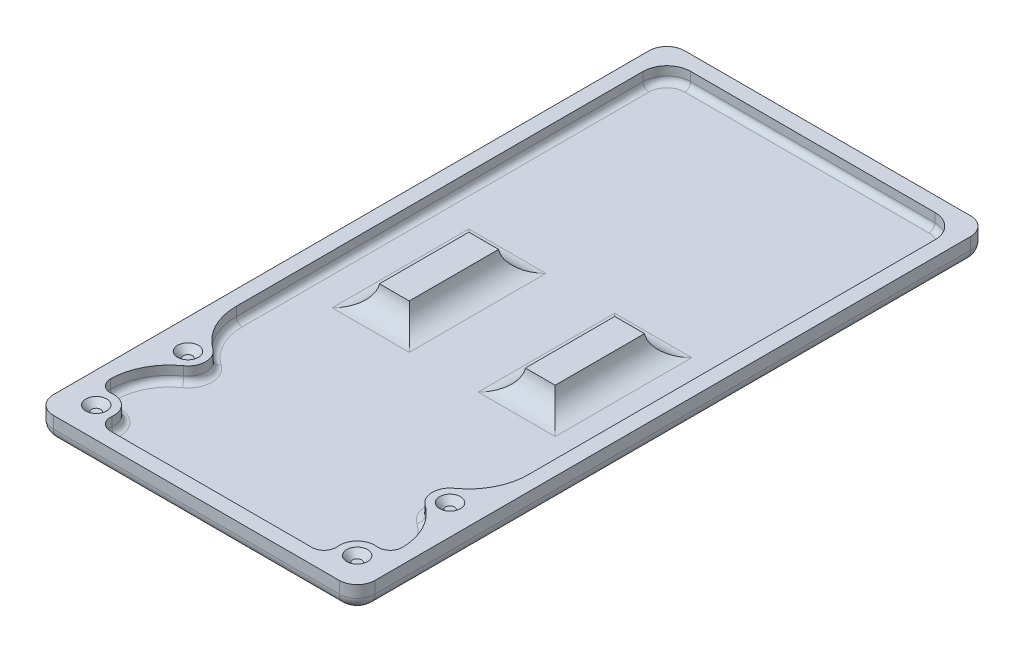
SolidWorks part; units mm, degrees
ref_plane "Front Plane" through (0, 0, 0) normal (0, 0, 1) x (1, 0, 0)
ref_plane "Top Plane" through (0, 0, 0) normal (0, 1, 0) x (1, 0, 0)
ref_plane "Right Plane" through (0, 0, 0) normal (1, 0, 0) x (0, 0, -1)
sketch "Sketch1" plane through (0, 0, 0) normal (0, 1, 0) x (1, 0, 0)
  line L1 (-24.5, -50.5) -> (24.5, -50.5)
  line L2 (-24.5, -50.5) -> (-24.5, 50.5)
  line L3 (-24.5, 50.5) -> (24.5, 50.5)
  line L4 (24.5, -50.5) -> (24.5, 50.5)
  line L5 (-24.5, -50.5) -> (24.5, 50.5) construction
  line L6 (-24.5, 50.5) -> (24.5, -50.5) construction
  point P0 (0, 0)
  dimension "D1" = 49
  dimension "D2" = 101
extrude "Boss-Extrude1" add sketch "Sketch1" along normal blind 1.5
sketch "Sketch2" plane through (0, 0, 0) normal (0, 1, 0) x (1, 0, 0)
  line L4 (24.5, -50.5) -> (24.5, 50.5)
  line L5 (24.5, 50.5) -> (-24.5, 50.5)
  line L6 (-24.5, 50.5) -> (-24.5, -50.5)
  line L7 (-24.5, -50.5) -> (24.5, -50.5)
  line L8 (24.5, -50.5) -> (24.5, 50.5)
  line L9 (24.5, 50.5) -> (-24.5, 50.5)
  line L10 (-24.5, 50.5) -> (-24.5, -50.5)
  line L11 (-24.5, -50.5) -> (24.5, -50.5)
  line L16 (27, -53) -> (27, 53)
  line L17 (27, 53) -> (-27, 53)
  line L18 (-27, 53) -> (-27, -53)
  line L19 (-27, -53) -> (27, -53)
  line L20 (27, -53) -> (27, 53)
  line L21 (27, 53) -> (-27, 53)
  line L22 (-27, 53) -> (-27, -53)
  line L23 (-27, -53) -> (27, -53)
  dimension "D1" = 0
  dimension "D2" = 2.5
extrude "Boss-Extrude2" add sketch "Sketch2" along normal blind 4
sketch "Sketch3" plane through (0, 0, 0) normal (0, 1, 0) x (1, 0, 0)
  line L0 (24.5, -50.5) -> (-24.5, -50.5) construction
  line L2 (-24.5, 50.5) -> (-24.5, -50.5) construction
  line L3 (-24.5, -30.7417) -> (-24.5, -34.0583)
  line L8 (-24.5, -46.4033) -> (-24.5, -50.5)
  line L9 (-24.5, 50.5) -> (-24.5, -50.5) construction
  line L10 (-24.5, -50.5) -> (-20.4033, -50.5)
  line L11 (-24.5, -50.5) -> (24.5, -50.5) construction
  arc A1 (-24.5, -34.0583) -> (-24.5, -30.7417) centre (-22, -32.4) ccw
  arc A2 (-20.4033, -50.5) -> (-24.5, -46.4033) centre (-21.9, -47.9) ccw
  dimension "D5" = 6
  dimension "D1" = 2.6
  dimension "D3" = 2.5
  dimension "D4" = 18.1
extrude "Boss-Extrude3" add sketch "Sketch3" along normal up to surface (4 mm away) up to face at (0, 4, 0)
sketch "Sketch8" plane through (0, 1.5, 0) normal (0, 1, 0) x (1, 0, 0)
  line L0 (0, 0) -> (-24.5, 0) construction
  line L1 (-14.75, 7.5) -> (-9.75, 7.5)
  line L2 (-14.75, 7.5) -> (-14.75, -7.5)
  line L3 (-14.75, -7.5) -> (-9.75, -7.5)
  line L4 (-9.75, 7.5) -> (-9.75, -7.5)
  line L5 (-24.5, 50.5) -> (-24.5, -30.7417) construction
  point P4 (-9.75, 0)
  point P11 (-12.25, 0)
  point P12 (-12.25, 7.5)
  dimension "D1" = 15
  dimension "D2" = 5
extrude "Boss-Extrude4" add sketch "Sketch8" along normal offset from surface (3.5 mm away) 1 up to face at (0, 4, 0) offset beyond the face yes
fillet "Fillet3" radius 4 4 edges at (-12.25, 1.5, -7.5) (-9.75, 1.5, 0) (-14.75, 1.5, 0) (-12.25, 1.5, 7.5)
mirror "Mirror1" about plane through (0, 0, 0) normal (1, 0, 0) of "Fillet3", "Boss-Extrude3", "Boss-Extrude4"
sketch "Sketch4" plane through (0, 4, 0) normal (0, 1, 0) x (1, 0, 0)
  circle A0 centre (-21.9, -47.9) radius 1.75
  circle A1 centre (21.9, -47.9) radius 1.75
  arc A2 (-20.4033, -50.5) -> (-24.5, -46.4033) centre (-21.9, -47.9) ccw construction
  arc A3 (24.5, -46.4033) -> (20.4033, -50.5) centre (21.9, -47.9) ccw construction
  dimension "D1" = 3.5
  dimension "D2" = 3.5
extrude "Cut-Extrude1" cut sketch "Sketch4" against normal blind 1
sketch "Sketch5" plane through (0, 4, 0) normal (0, 1, 0) x (1, 0, 0)
  circle A0 centre (-22, -32.4) radius 1.75
  circle A1 centre (22, -32.4) radius 1.75
  dimension "D1" = 3.5
  dimension "D2" = 3.5
extrude "Cut-Extrude2" cut sketch "Sketch5" against normal blind 1
sketch "Sketch6" plane through (0, 0, 0) normal (0, 1, 0) x (1, 0, 0)
  line L1 (-9, -45) -> (5.5, -45)
  line L2 (-9, -45) -> (-9, -52.3)
  line L3 (-9, -52.3) -> (5.5, -52.3)
  line L4 (5.5, -45) -> (5.5, -52.3)
  line L8 (-20.4033, -50.5) -> (20.4033, -50.5) construction
  line L10 (24.5, -46.4033) -> (24.5, -34.0583) construction
  line L11 (-24.5, -34.0583) -> (-24.5, -46.4033) construction
  line L13 (-27, -53) -> (27, -53) construction
  dimension "D1" = 15.5
  dimension "D2" = 19
  dimension "D3" = 0.7
  dimension "D4" = 5.5
extrude "Cut-Extrude3" [suppressed] cut sketch "Sketch6" along normal through all
sketch "Sketch7" plane through (0, 0, 0) normal (0, 1, 0) x (1, 0, 0)
  line L0 (-27, -53) -> (27, -53) construction
  line L1 (18.3, -47.7) -> (6.5, -47.7)
  line L2 (18.3, -47.7) -> (18.3, -43.7)
  line L3 (18.3, -43.7) -> (6.5, -43.7)
  line L4 (6.5, -47.7) -> (6.5, -43.7)
  line L6 (-27, -53) -> (27, -53) construction
  line L7 (27, -53) -> (27, 53) construction
  point P10 (12.4, -43.7)
  dimension "D1" = 11.8
  dimension "D3" = 9.3
  dimension "D4" = 5.3
  dimension "D5" = 14.6
extrude "Cut-Extrude4" [suppressed] cut sketch "Sketch7" along normal through all
fillet "Fillet1" radius 3 4 edges at (-27, 2, 53) (27, 2, 53) (27, 2, -53) (-27, 2, -53)
fillet "Fillet2" radius 10 4 edges at (24.5, 2.75, 30.7417) (24.5, 2.75, 34.0583) (-24.5, 2.75, 30.7417) (-24.5, 2.75, 34.0583)
chamfer "Chamfer1" distance 1 angle 45 2 edges at (-22, 3, 34.15) (22, 3, 34.15)
chamfer "Chamfer2" distance 1 angle 45 2 edges at (-21.9, 3, 49.65) (21.9, 3, 49.65)
fillet "Fillet4" radius 2 4 edges at (24.5, 2.75, 46.4033) (20.4033, 2.75, 50.5) (-20.4033, 2.75, 50.5) (-24.5, 2.75, 46.4033)
fillet "Fillet6" radius 4 2 edges at (24.5, 2.75, -50.5) (-24.5, 2.75, -50.5)
fillet "Fillet5" radius 1 3 edges at (24.5, 1.5, -12.3592) (0, 1.5, -50.5) (-24.5, 1.5, -12.3592) type face fillet first side face at (12.25, 1.5, 0) second side face at (24.5, 2.75, -12.3592) second side face at (0, 2.75, -50.5) second side face at (-24.5, 2.75, -12.3592)
fillet "Fillet7" radius 2 8 edges at (-26.1213, 0, -52.1213) (0, 0, -53) (26.1213, 0, -52.1213) (27, 0, 0) (26.1213, 0, 52.1213) (0, 0, 53) (-26.1213, 0, 52.1213) (-27, 0, 0)
sketch "Sketch9" plane through (0, 0, 0) normal (0, 1, 0) x (1, 0, 0)
  line L1 (-50, 75) -> (50, 75)
  line L2 (-50, 75) -> (-50, -75)
  line L3 (-50, -75) -> (50, -75)
  line L4 (50, 75) -> (50, -75)
  line L5 (-50, 75) -> (50, -75) construction
  line L6 (-50, -75) -> (50, 75) construction
  point P0 (0, 0)
  dimension "D1" = 150
  dimension "D2" = 100
extrude "Boss-Extrude5" [suppressed] add sketch "Sketch9" along normal blind 10 separate body
combine bodies "Combine1" [suppressed] operation type subtract main body 110 bodies to subtract 106
sketch "Sketch10" [suppressed] plane through (0, 4, 0) normal (0, 1, 0) x (1, 0, 0)
  line L1 (-50, 75) -> (50, 75)
  line L2 (-50, 75) -> (-50, -75)
  line L3 (-50, -75) -> (50, -75)
  line L4 (50, 75) -> (50, -75)
  line L5 (-50, 75) -> (50, -75) construction
  line L6 (-50, -75) -> (50, 75) construction
  point P0 (0, 0)
  dimension "D1" = 100
  dimension "D2" = 150
extrude "Boss-Extrude6" [suppressed] add sketch "Sketch10" against normal blind 10
combine bodies "Combine2" [suppressed] operation type subtract main body 115 bodies to subtract 106
sketch "Sketch13" [suppressed] plane through (0, 4, 0) normal (0, 1, 0) x (1, 0, 0)
  line L0 (20.5, 50.5) -> (-20.5, 50.5) construction
  line L1 (-24.5, 46.5) -> (-24.5, -50.5) construction
  line L2 (-24.5, -50.5) -> (24.5, -50.5) construction
  line L3 (24.5, 46.5) -> (24.5, -50.5) construction
  line L4 (20.5, 50.5) -> (-20.5, 50.5)
  line L5 (-24.5, 46.5) -> (-24.5, -50.5)
  line L6 (-24.5, -50.5) -> (24.5, -50.5)
  line L7 (24.5, 46.5) -> (24.5, -50.5)
  arc A1 (-20.5, 50.5) -> (-24.5, 46.5) centre (-20.5, 46.5) ccw construction
  arc A2 (24.5, 46.5) -> (20.5, 50.5) centre (20.5, 46.5) ccw construction
  arc A3 (-20.5, 50.5) -> (-24.5, 46.5) centre (-20.5, 46.5) ccw
  arc A4 (24.5, 46.5) -> (20.5, 50.5) centre (20.5, 46.5) ccw
extrude "Boss-Extrude8" [suppressed] add sketch "Sketch13" against normal up to surface (4 mm away)
scale "Scale1" [suppressed]
sketch "Sketch12" [suppressed] plane through (0, 3.9802, 0) normal (0, 1, 0) x (1, 0, 0)
  line L1 (-50, -75) -> (50, -75)
  line L2 (-50, -75) -> (-50, 75)
  line L3 (-50, 75) -> (50, 75)
  line L4 (50, -75) -> (50, 75)
  line L5 (-50, -75) -> (50, 75) construction
  line L6 (-50, 75) -> (50, -75) construction
  point P0 (0, 0)
  dimension "D1" = 150
  dimension "D2" = 100
extrude "Boss-Extrude7" [suppressed] add sketch "Sketch12" along normal blind 3
